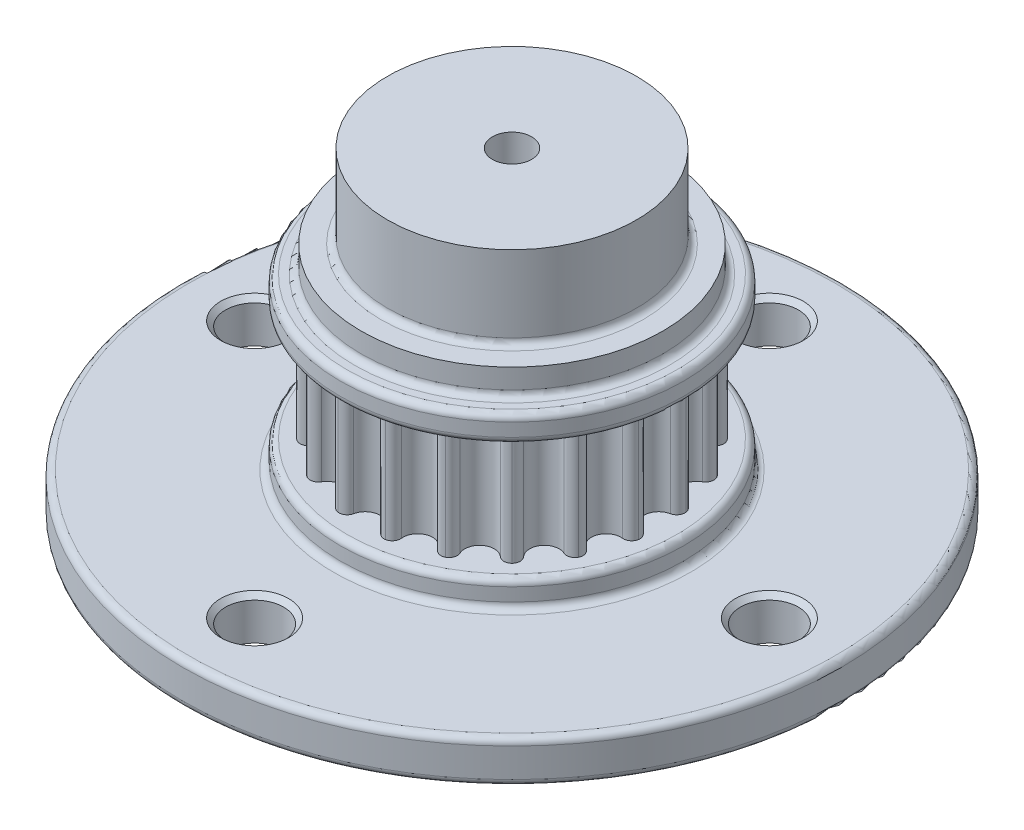
SolidWorks part; units mm, degrees
ref_plane "Front Plane" through (0, 0, 0) normal (0, 0, 1) x (1, 0, 0)
ref_plane "Top Plane" through (0, 0, 0) normal (0, 1, 0) x (1, 0, 0)
ref_plane "Right Plane" through (0, 0, 0) normal (1, 0, 0) x (0, 0, -1)
ref_plane "Plane1" through (0, 0, 0) normal (-0.7071, 0, 0.7071) x (0.7071, 0, 0.7071)
sketch "Sketch1" plane through (0, 0, 0) normal (0, 1, 0) x (1, 0, 0)
  line L0 (0, 0) -> (0, 9.1676) construction
  line L1 (0, 0) -> (2.731, 8.405) construction
  circle A0 centre (0, 0) radius 9.1676 construction
  circle A1 centre (0, 0) radius 7.9476 construction
  circle A2 centre (0, 8.8376) radius 0.89 construction
  circle A5 centre (2.731, 8.405) radius 0.89 construction
  arc A6 (0, 7.9476) -> (0.8721, 8.6598) centre (0, 8.8376) ccw
  arc A7 (0.8721, 8.6598) -> (1.4405, 9.0537) centre (1.362, 8.5599) cw
  arc A8 (1.4277, 9.0557) -> (1.8466, 8.5054) centre (1.3498, 8.5618) cw
  arc A9 (2.4559, 7.5586) -> (1.8466, 8.5054) centre (2.731, 8.405) cw
  arc A10 (1.4405, 9.0537) -> (1.4277, 9.0557) centre (0, 0) cw
  arc A11 (0, 7.9476) -> (2.4559, 7.5586) centre (0, 0) ccw
  dimension "D1" = 18.3352
  dimension "D3" = 1.78
  dimension "D4" = 0.5
  dimension "D2" = 1.22
  dimension "D5" = 18
extrude "Boss-Extrude1" add sketch "Sketch1" along normal mid plane 7.112 contours A6 A11 A9 A8 A7 region at (0.0089, 0, -0.0564)
ref_axis "Axis1" through (0, 3.3, 0) along (0, -1, 0)
pattern_circular "CirPattern1" count 20 over 360 about axis through (0, 3.3, 0) along (0, -1, 0) of "Boss-Extrude1"
sketch "Sketch2" plane through (0, 0, 0) normal (1, 0, 0) x (0, 0, -1)
  line L10 (0, 3.5) -> (10.3423, 3.5) construction
  line L11 (0, 3.5) -> (0, 5.0875) construction
  line L12 (0, 5.0875) -> (10.3423, 5.0875)
  line L15 (10.3423, 3.5) -> (10.3423, 5.0875) construction
  line L20 (0, 3.3) -> (0, -3.3) construction
  line L22 (10.3423, 5.0875) -> (0, 5.0875) construction
  line L23 (10.3423, 5.0875) -> (10.3423, 3.5)
  line L24 (10.3423, 3.5) -> (0, 3.5)
  line L25 (0, 5.0875) -> (0, 3.5)
  dimension "D1" = 1.5875
  dimension "D2" = 10.3423
  dimension "D3" = 3.5
revolve "Revolve3" add sketch "Sketch2" angle 360 about axis through (0, 3.3, 0) along (0, -1, 0) region at (0, 4.2937, -5.1712)
mirror "Mirror1" about plane through (0, 0, 0) normal (0, 1, 0) of "Revolve3"
sketch "Sketch9" plane through (0, -5.0875, 0) normal (0, -1, 0) x (1, 0, 0)
  circle A0 centre (0, 0) radius 19.8438
  circle A1 centre (0, 0) radius 1.5
  dimension "D1" = 3
  dimension "D2" = 39.6875
extrude "Boss-Extrude2" add sketch "Sketch9" along normal blind 2.54
sketch "Sketch3" plane through (0, 0, 0) normal (0, 1, 0) x (1, 0, 0)
  circle A0 centre (-15.5, 0) radius 1.7462
  circle A3 centre (0, 15.5) radius 1.7462
  circle A4 centre (15.5, 0) radius 1.7463
  circle A5 centre (0, -15.5) radius 1.7462
  dimension "D3" = 3.4925
  dimension "D1" = 15.5
  dimension "D4" = 4
extrude "Cut-Extrude1" cut sketch "Sketch3" against normal through all both and the other way through all
ref_axis "Axis2" through (-15.5, -7.6275, 0) along (0, 1, 0)
sketch "Sketch6" plane through (0, 0, 0) normal (0, 0, 1) x (1, 0, 0)
  line L0 (-19.1322, -3.5) -> (-11.8678, -3.5) construction
  line L1 (-5.7956, -3.5) -> (-6.4824, -3.5) construction
  line L2 (-11.8678, -3.5) -> (-15.5, -7.1322)
  line L3 (-15.5, -7.1322) -> (-19.1322, -3.5) construction
  line L4 (-18.548, -4.0842) -> (-12.452, -4.0842) construction
  line L5 (-17.2462, -3.998) -> (-13.7538, -3.998) construction
  line L8 (-15.5, -7.1322) -> (-15.5, -3.5)
  line L9 (-15.5, -3.5) -> (-11.8678, -3.5)
  line L10 (-15.5, -7.6275) -> (-15.5, -5.0875) construction
  line L12 (-17.2462, -5.0875) -> (-17.2462, -7.6275) construction
  line L13 (-13.7538, -7.6275) -> (-13.7538, -5.0875) construction
  point P2 (-15.5, -3.998)
  dimension "D1" = 6.096
  dimension "D2" = 0.5842
revolve "Cut-Revolve2" cut sketch "Sketch6" angle 360 about axis through (-15.5, -7.6275, 0) along (0, 1, 0)
pattern_circular "CirPattern2" count 4 over 360 about axis through (0, 3.3, 0) along (0, -1, 0) of "Cut-Revolve2"
sketch "Sketch11" plane through (0, -5.0875, 0) normal (0, -1, 0) x (1, 0, 0)
  circle A0 centre (0, 0) radius 1.5
  dimension "D1" = 3
extrude "Cut-Extrude2" cut sketch "Sketch11" against normal blind 6
sketch "Sketch10" plane through (0, 0, 0) normal (1, 0, 0) x (0, 0, -1)
  line L1 (1.1822, 6.675) -> (7.5, 6.675) construction
  line L2 (1.1822, 6.675) -> (1.1822, 11.675)
  line L3 (1.1822, 11.675) -> (7.5, 11.675)
  line L4 (7.5, 6.675) -> (7.5, 11.675)
  line L5 (0, 0) -> (0, 11.675) construction
  line L6 (10.3423, 5.0875) -> (-10.3423, 5.0875) construction
  line L7 (1.1822, 6.675) -> (9.0875, 6.675) construction
  line L8 (1.1822, 6.675) -> (1.1822, 5.0875)
  line L9 (1.1822, 5.0875) -> (9.0875, 5.0875)
  line L10 (9.0875, 6.675) -> (9.0875, 5.0875)
  line L11 (7.5, 6.675) -> (9.0875, 6.675)
  line L12 (0, 11.675) -> (1.1822, 11.675) construction
  dimension "D1" = 2.3644
  dimension "D2" = 5
  dimension "D3" = 1.5875
  dimension "D4" = 1.5875
  dimension "D5" = 15
revolve "Revolve4" add sketch "Sketch10" angle 360 about L5
fillet "Fillet1" radius 0.3969 8 edges at (0, 5.0875, 10.3423) (0, 3.5, 10.3423) (0, -7.6275, -19.8438) (0, -5.0875, -19.8438) (0, 6.675, -7.5) (0, 5.0875, -9.0875) (0, -3.5, 10.3423) (0, -5.0875, 10.3423)
equation "\"TEETH_NUM\"= 20"
equation "\"TOOTH_PITCH\"= 3mm"
equation "\"PITCH_LINE_OFFSET\"= .015in"
equation "\"DIAMETER_PER_GROOVE\"= \"OUTSIDE_DIAMETER\" / \"TEETH_NUM\" * 1in"
equation "\"PITCH_DIAMETER\"= ( ( \"TEETH_NUM\" * 3 - 1.31 ) / 3.1415 + .415 ) * 1mm"
equation "\"OUTSIDE_DIAMETER\"= \"PITCH_DIAMETER\" - \"PITCH_LINE_OFFSET\" * 2"
equation "\"D1@Sketch1\"=\"OUTSIDE_DIAMETER\""
equation "\"TOOTH_HEIGHT\"= 1.22mm"
equation "\"D2@Sketch1\"=\"TOOTH_HEIGHT\""
equation "\"TOOTH_DIAMETER\"= 1.78mm"
equation "\"INTERNAL_RADIUS\"= .5mm"
equation "\"D3@Sketch1\"=\"TOOTH_DIAMETER\""
equation "\"D5@Sketch1\"=360 / \"TEETH_NUM\""
equation "\"D4@Sketch1\"=\"INTERNAL_RADIUS\""
equation "\"D1@CirPattern1\"=\"TEETH_NUM\""
equation "\"BELT_GAP\"= 7mm"
equation "\"D2@Sketch2\"=\"PITCH_DIAMETER\"/2+1/32"
equation "\"D3@Sketch2\"=\"BELT_GAP\"/2"
